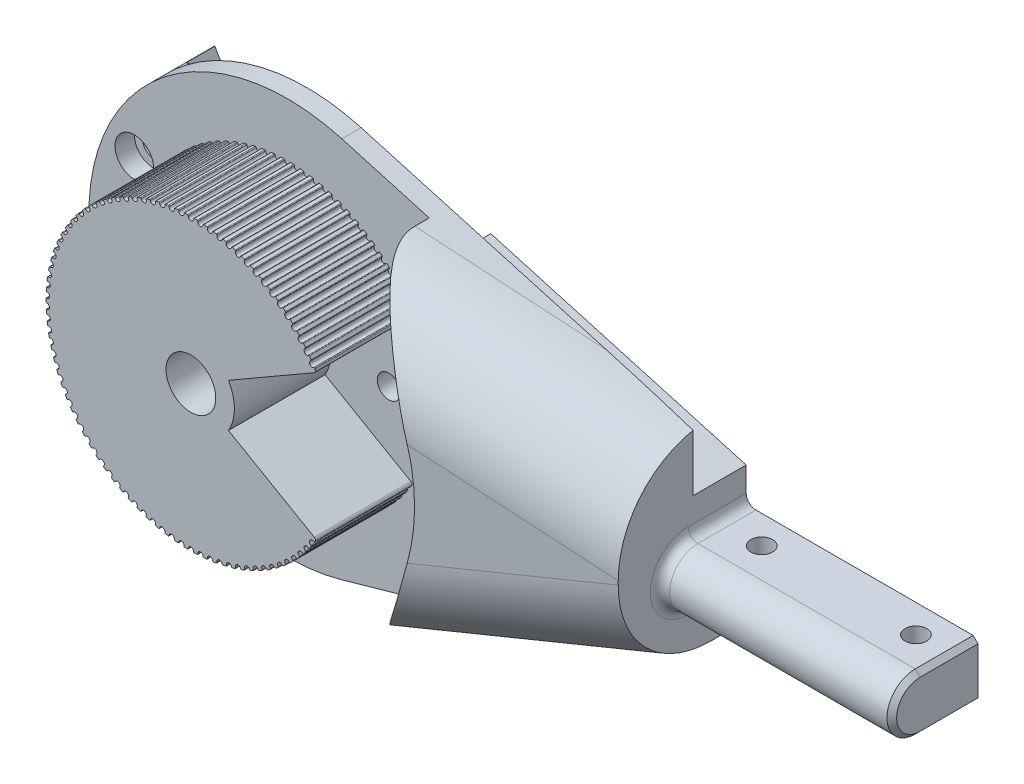
SolidWorks part; units mm, degrees
ref_plane "Plano frontal" through (0, 0, 0) normal (0, 0, 1) x (1, 0, 0)
ref_plane "Plano superior" through (0, 0, 0) normal (0, 1, 0) x (1, 0, 0)
ref_plane "Plano direito" through (0, 0, 0) normal (1, 0, 0) x (0, 0, -1)
sketch "Esboço1" plane through (0, 0, 0) normal (0, 0, 1) x (1, 0, 0)
  line L0 (208.8814, 100) -> (344.5645, 100) construction
  line L1 (288.8814, 120) -> (288.8814, 80)
  line L2 (288.8814, 120) -> (220.128, 139.5506)
  line L3 (288.8814, 80) -> (220.128, 60.4494)
  arc A0 (220.128, 139.5506) -> (220.128, 60.4494) centre (208.8814, 100) ccw
  arc A3 (241.5271, 125) -> (213.2304, 140.888) centre (208.8814, 100) ccw construction
  dimension "D2" = 20
  dimension "D1" = 20
  dimension "D3" = 80
extrude "Ressalto-extrusão1" add sketch "Esboço1" along normal up to surface (35 mm away)
sketch "Esboço2" plane through (0, 0, 35) normal (0, 0, 1) x (1, 0, 0)
  circle A0 centre (208.8814, 100) radius 45.2239
  circle A1 centre (208.8814, 100) radius 30
  dimension "D1" = 60
extrude "Corte-extrusão1" cut sketch "Esboço2" against normal blind 20
sketch "Esboço3" plane through (0, 0, 35) normal (0, 0, 1) x (1, 0, 0)
  line L3 (208.8814, 100) -> (208.8814, 130) construction
  line L4 (208.3314, 129.8) -> (208.3314, 129.995)
  line L5 (209.4314, 129.8) -> (209.4314, 129.995)
  line L6 (208.8814, 100) -> (206.8671, 129.9323) construction
  arc A4 (208.3314, 129.8) -> (209.4314, 129.8) centre (208.8814, 129.8) ccw
  circle A5 centre (208.8814, 100) radius 30 construction
  circle A6 centre (208.8814, 100) radius 30 construction
  arc A12 (209.4314, 129.995) -> (208.3314, 129.995) centre (208.8814, 100) ccw
  dimension "D1" = 1.1
  dimension "D2" = 0.75
  dimension "D5" = 3.85
extrude "Corte-extrusão2" cut sketch "Esboço3" against normal up to surface (20 mm away) up to face at (238.8814, 100, 15)
ref_axis "Eixo1" through (208.8814, 100, 15) along (0, 0, 1)
chamfer "Chanfro1" distance 40 angle 12 1 edges at (288.8814, 100, 35) first distance on face at (267.5264, 100, 35)
fillet "Filete4" radius 20 2 edges at (268.8814, 125.6872, 30.7489) (268.8814, 74.3128, 30.7489)
sketch "Esboço6" plane through (0, 0, 0) normal (0, 0, -1) x (-1, 0, 0)
  line L3 (-245.2234, 138.9462) -> (-219.2737, 94)
  line L4 (-172.5394, 138.9462) -> (-245.2234, 138.9462)
  line L5 (-198.4891, 94) -> (-172.5394, 138.9462)
  line L6 (-245.2234, 138.9462) -> (-219.2737, 94)
  line L7 (-172.5394, 138.9462) -> (-245.2234, 138.9462)
  line L8 (-198.4891, 94) -> (-172.5394, 138.9462)
  arc A1 (-219.2737, 94) -> (-198.4891, 94) centre (-208.8814, 100) ccw
  arc A2 (-219.2737, 94) -> (-198.4891, 94) centre (-208.8814, 100) ccw
  dimension "D1" = 0
extrude "Corte-extrusão5" cut sketch "Esboço6" against normal blind 6
sketch "Esboço8" plane through (0, 0, 0) normal (0, 0, -1) x (-1, 0, 0)
  line L4 (-295.6181, 106.0005) -> (-179.1715, 139.1131)
  line L5 (-295.6181, 136.4235) -> (-295.6181, 106.0005)
  line L6 (-188.9482, 165.3081) -> (-295.6181, 136.4235)
  line L7 (-179.1715, 139.1131) -> (-188.9482, 165.3081)
  line L8 (-344.3191, 92.152) -> (-179.1715, 139.1131)
  line L9 (-312.4123, 131.8759) -> (-344.3191, 92.152)
  line L10 (-188.9482, 165.3081) -> (-312.4123, 131.8759)
  line L11 (-179.1715, 139.1131) -> (-188.9482, 165.3081)
  line L32 (-288.8814, 120) -> (-241.9842, 133.3356) construction
  dimension "D1" = 0
extrude "Corte-extrusão6" cut sketch "Esboço8" against normal blind 11
chamfer "Chanfro2" distance 10 angle 31 1 edges at (189.3926, 136.2067, 8.5) first distance on face at (238.0885, 122.3596, 5.6667)
sketch "Esboço9" plane through (288.8814, 0, 0) normal (1, 0, 0) x (0, 0, -1)
  line L7 (-12, 100.85) -> (0, 100.85)
  line L8 (0, 89.15) -> (-12, 89.15)
  line L9 (0, 80) -> (0, 107.9162) construction
  line L10 (0, 89.15) -> (0, 100.85)
  arc A2 (-12, 100.85) -> (-12, 89.15) centre (-12, 95) ccw
  dimension "D1" = 12
extrude "Ressalto-extrusão2" add sketch "Esboço9" along normal blind 48
fillet "Filete5" radius 2 3 edges at (288.8814, 89.15, 6) (288.8814, 95, 17.85) (288.8814, 100.85, 6)
chamfer "Chanfro3" distance 1 angle 45 3 edges at (336.8814, 100.85, 6) (336.8814, 95, 17.85) (336.8814, 89.15, 6)
sketch "Esboço10" plane through (0, 100.85, 0) normal (0, 1, 0) x (1, 0, 0)
  circle A0 centre (329.8463, -5.82) radius 2.25
  circle A1 centre (297.91, -5.82) radius 2.25
extrude "Corte-extrusão7" cut sketch "Esboço10" against normal through all
sketch "Esboço11" plane through (0, 0, 0) normal (0, 0, -1) x (-1, 0, 0)
  circle A0 centre (-208.8814, 100) radius 5.15
  dimension "D1" = 10.3
extrude "Corte-extrusão8" cut sketch "Esboço11" against normal through all
hole_wizard "Rebaixo para SHCS M41" positions "Esboço17" profile "Esboço18" counterbore size "M4" standard "Ansi Metric" end condition through all
sketch "Esboço17" plane through (0, 0, 15) normal (0, 0, 1) x (1, 0, 0)
  point P0 (177.163, 114.7967)
  point P2 (208.8814, 65)
  point P4 (240.5998, 114.7967)
  dimension "D1" = 63.4368
  dimension "D2" = 35
  dimension "D3" = 14.7967
sketch "Esboço18" plane through (177.163, 114.7967, 15) normal (1, 0, 0) x (0, -1, 0)
  line L0 (0, 0) -> (0, 15)
  line L1 (0, 15) -> (2.25, 15)
  line L3 (2.25, 15) -> (2.25, 4)
  line L4 (2.25, 4) -> (4, 4)
  line L5 (4, 4) -> (4, 0)
  line L7 (4, 0) -> (0, 0)
  line L11 (0, -6.35) -> (0, 107.95) construction
  dimension "Thru Hole Dia." = 4.5
  dimension "Thru Hole Depth" = 15
  dimension "C'Bore Dia." = 8
  dimension "C'Bore Depth" = 4
sketch "Esboço19" plane through (0, 0, 35) normal (0, 0, 1) x (1, 0, 0)
  line L0 (208.8814, 100) -> (251.418, 100) construction
  line L1 (208.8814, 100) -> (241.9756, 119.107) construction
  line L2 (208.8814, 100) -> (240.6422, 81.6629) construction
  line L3 (216.6756, 104.5) -> (234.8622, 115)
  line L4 (216.6756, 95.5) -> (234.8622, 85)
  arc A2 (234.8622, 85) -> (234.8622, 115) centre (208.8814, 100) ccw
  arc A3 (216.6756, 95.5) -> (216.6756, 104.5) centre (208.8814, 100) ccw
  dimension "D3" = 18
  dimension "D4" = 30
  dimension "D1" = 30
  dimension "D2" = 30
extrude "Corte-extrusão9" cut sketch "Esboço19" against normal up to surface (20 mm away) up to face at (181.163, 114.7967, 15)
fillet "Filete7" radius 0.5 2 edges at (234.8622, 85, 25) (234.8622, 115, 25)
sketch "Esboço20" plane through (0, 0, 15) normal (0, 0, 1) x (1, 0, 0)
  circle A0 centre (229.8814, 100) radius 2.4
  dimension "D1" = 4.8
  dimension "D2" = 21
extrude "Corte-extrusão10" cut sketch "Esboço20" against normal through all
ref_plane "Plano1" through (0, 100, 0) normal (0, -1, 0) x (-1, 0, 0)
fillet "Filete8" radius 0.15 2 edges at (208.3314, 129.995, 25) (209.4314, 129.995, 25)
pattern_circular "PadrãoCircular3" count 94 every 3.83 about axis through (208.8814, 100, 15) along (0, 0, 1) skipping 63, 64, 65, 66, 67, 68, 69, 70, 71, 72, 73, 74, 75, 76, 77, 78 of "Corte-extrusão2", "Filete8"
